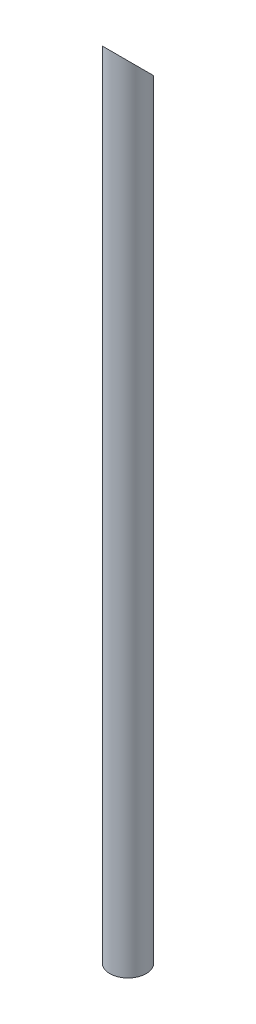
SolidWorks part; units mm, degrees
ref_plane "Front Plane" through (0, 0, 0) normal (0, 0, 1) x (1, 0, 0)
ref_plane "Top Plane" through (0, 0, 0) normal (0, 1, 0) x (1, 0, 0)
ref_plane "Right Plane" through (0, 0, 0) normal (1, 0, 0) x (0, 0, -1)
sketch "Sketch1" plane through (0, 0, 0) normal (0, 1, 0) x (1, 0, 0)
  circle A0 centre (0, 0) radius 15.9
extrude "Boss-Extrude2" add sketch "Sketch1" along normal blind 700
sketch "Sketch2" plane through (0, 0, 0) normal (1, 0, 0) x (0, 0, -1)
  line L0 (15.9, 0) -> (15.9, 700) construction
  line L1 (-15.9, 700) -> (15.9, 700)
  line L2 (-15.9, 700) -> (-15.9, 668.2)
  line L3 (-15.9, 668.2) -> (15.9, 668.2)
  line L4 (15.9, 700) -> (15.9, 668.2)
  line L5 (-15.9, 700) -> (15.9, 668.2)
  line L6 (-15.9, 700) -> (15.9, 668.2)
  dimension "D1" = 31.8
extrude "Cut-Extrude1" cut sketch "Sketch2" against normal through all and the other way through all contours L1 L5 L4 region at (0, 689.4, -5.3)
